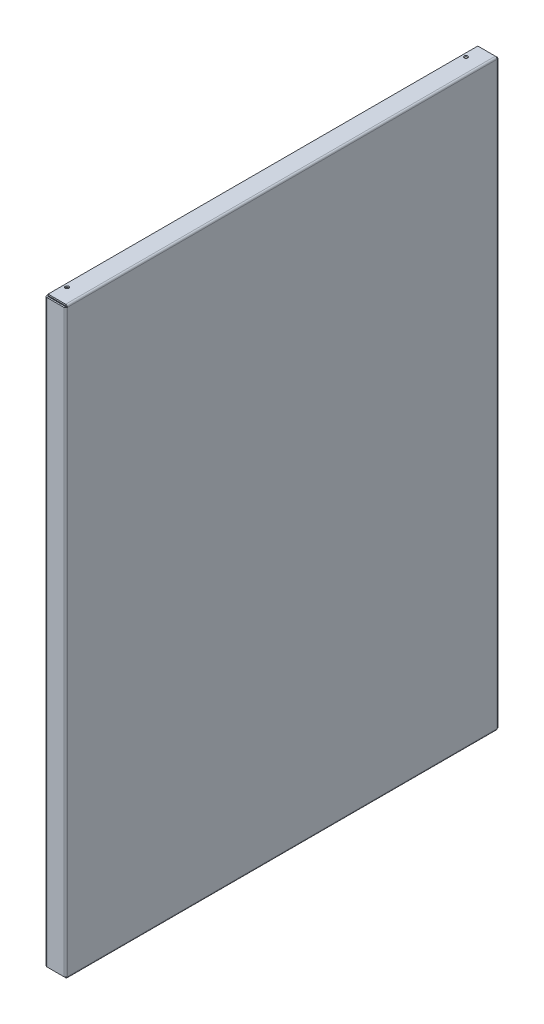
SolidWorks part; units mm, degrees
note: The reader was unsure of these and kept them because the rebuilt part matched: flange length of "Edge-Flange1", "Edge-Flange3", "Edge-Flange4", "Edge-Flange5", "Edge-Flange6", "Edge-Flange7", "Edge-Flange8", "Edge-Flange9".
material "Chrome Stainless Steel"
ref_plane "Front Plane" through (0, 0, 0) normal (0, 0, 1) x (1, 0, 0)
ref_plane "Top Plane" through (0, 0, 0) normal (0, 1, 0) x (1, 0, 0)
ref_plane "Right Plane" through (0, 0, 0) normal (1, 0, 0) x (0, 0, -1)
sketch "Sketch2" plane through (0, 0, 0) normal (1, 0, 0) x (0, 0, -1)
  line L1 (-300, 406) -> (300, 406)
  line L2 (-300, 406) -> (-300, -406)
  line L3 (-300, -406) -> (300, -406)
  line L4 (300, 406) -> (300, -406)
  line L5 (-300, 406) -> (300, -406) construction
  line L6 (-300, -406) -> (300, 406) construction
  point P0 (0, 0)
  dimension "D1" = 600
  dimension "D2" = 812
base flange "Base-Flange1" sketch "Sketch2" thickness 2 reverse thickness direction no parameters "D1"=6.35
edge flange "Edge-Flange1" sketch "Sketch9" flange angle 90 flange length 25 flange position material inside bend radius 0.5 thickness 2 relief rectangular parameters "D6"=10
sketch "Sketch9" plane through (-2, 406, 0) normal (0, -1, 0) x (0, 0, 1)
  line L2 (-300, 0) -> (-300, 25)
  line L3 (-300, 25) -> (300, 25)
  line L4 (300, 25) -> (300, 0)
  line L9 (300, 0) -> (-300, 0) construction
  line L10 (300, 0) -> (-300, 0)
bend "EdgeBend1" bend radius 0.5 bend angle 90 parameters "D5"=1
edge flange "Edge-Flange3" sketch "Sketch15" flange angle 90 flange length 25 flange position bend outside bend radius 0.5 thickness 2 relief rectangular parameters "D6"=10
sketch "Sketch15" plane through (-2, 0, 300) normal (0, 0, 1) x (0, 1, 0)
  line L0 (403.5, 0) -> (-406, 0) construction
  line L1 (403.5, 0) -> (-406, 0)
  line L2 (-406, 0) -> (-406, 25)
  line L3 (-406, 25) -> (403.5, 25)
  line L4 (403.5, 25) -> (403.5, 0)
bend "EdgeBend3" bend radius 0.5 bend angle 90 parameters "D5"=2
edge flange "Edge-Flange4" sketch "Sketch18" flange angle 90 flange length 25 flange position bend outside bend radius 0.5 thickness 2 relief rectangular parameters "D6"=10
sketch "Sketch18" plane through (-2, 0, -300) normal (0, 0, -1) x (0, -1, 0)
  line L2 (-403.5, 0) -> (-403.5, 25)
  line L3 (-403.5, 25) -> (406, 25)
  line L4 (406, 25) -> (406, 0)
  line L11 (406, 0) -> (-403.5, 0) construction
  line L12 (406, 0) -> (-403.5, 0)
bend "EdgeBend4" bend radius 0.5 bend angle 90 parameters "D5"=3
edge flange "Edge-Flange5" sketch "Sketch21" flange angle 90 flange length 25 flange position bend outside bend radius 0.5 thickness 2 relief rectangular parameters "D6"=10
sketch "Sketch21" plane through (-2, -406, 0) normal (0, -1, 0) x (0, 0, 1)
  line L2 (-300, 0) -> (-300, 25)
  line L3 (-300, 25) -> (300, 25)
  line L4 (300, 25) -> (300, 0)
  line L7 (300, 0) -> (-300, 0) construction
  line L8 (300, 0) -> (-300, 0)
bend "EdgeBend5" bend radius 0.5 bend angle 90 parameters "D5"=4
sketch "Sketch22" plane through (0, -408.5, 0) normal (0, -1, 0) x (1, 0, 0)
  line L0 (-27, 300) -> (-27, -300) construction
  line L2 (-2.5, 300) -> (-27, 300) construction
  circle A0 centre (-22, 278.5) radius 2.5
  dimension "D1" = 5
  dimension "D2" = 5
  dimension "D3" = 21.5
extrude "Cut-Extrude1" cut sketch "Sketch22" against normal through all normal cut yes
sketch "Sketch23" plane through (0, 406, 0) normal (0, 1, 0) x (1, 0, 0)
  line L1 (-27, 300) -> (-2.5, 300) construction
  line L3 (-27, -300) -> (-27, 300) construction
  circle A0 centre (-22, 278.5) radius 2.5
  dimension "D1" = 5
  dimension "D2" = 21.5
  dimension "D3" = 5
extrude "Cut-Extrude2" cut sketch "Sketch23" against normal through all normal cut yes
sketch "Sketch24" plane through (0, 0, -302.5) normal (0, 0, -1) x (-1, 0, 0)
  line L0 (27, -406) -> (27, 403.5) construction
  line L1 (2.5, -406) -> (27, -406) construction
  line L2 (27, 403.5) -> (2.5, 403.5) construction
  circle A0 centre (22, 382) radius 2.5
  circle A1 centre (22, -384.5) radius 2.5
  dimension "D1" = 5
  dimension "D4" = 5
  dimension "D2" = 5
  dimension "D3" = 5
  dimension "D5" = 21.5
  dimension "D6" = 21.5
extrude "Cut-Extrude3" cut sketch "Sketch24" against normal blind 25 normal cut yes
edge flange "Edge-Flange6" sketch "Sketch27" flange angle 90 flange length 10 flange position material outside bend radius 1 thickness 2 relief rectangular parameters "D6"=10
sketch "Sketch27" plane through (-27, 0, -300.5) normal (1, 0, 0) x (0, 1, 0)
  line L2 (-406, 0) -> (-406, 10)
  line L3 (-406, 10) -> (403.5, 10)
  line L4 (403.5, 10) -> (403.5, 0)
  line L5 (403.5, 0) -> (-406, 0) construction
  line L6 (403.5, 0) -> (-406, 0)
bend "EdgeBend6" bend radius 1 bend angle 90 parameters "D5"=5
edge flange "Edge-Flange7" sketch "Sketch30" flange angle 90 flange length 20 flange position material outside bend radius 1 thickness 2 relief rectangular parameters "D6"=10
sketch "Sketch30" plane through (-27, 0, -290.5) normal (0, 0, -1) x (0, 1, 0)
  line L2 (-406, 0) -> (-406, 20)
  line L3 (-406, 20) -> (403.5, 20)
  line L4 (403.5, 20) -> (403.5, 0)
  line L9 (403.5, 0) -> (-406, 0) construction
  line L10 (403.5, 0) -> (-406, 0)
bend "EdgeBend7" bend radius 1 bend angle 90 parameters "D5"=6
edge flange "Edge-Flange8" sketch "Sketch33" flange angle 90 flange length 10 flange position material outside bend radius 1 thickness 2 relief rectangular parameters "D6"=10
sketch "Sketch33" plane through (-27, 0, 300.5) normal (1, 0, 0) x (0, -1, 0)
  line L2 (-403.5, 0) -> (-403.5, 10)
  line L3 (-403.5, 10) -> (406, 10)
  line L4 (406, 10) -> (406, 0)
  line L5 (406, 0) -> (-403.5, 0) construction
  line L6 (406, 0) -> (-403.5, 0)
bend "EdgeBend8" bend radius 1 bend angle 90 parameters "D5"=7
edge flange "Edge-Flange9" sketch "Sketch36" flange angle 90 flange length 20 flange position material outside bend radius 1 thickness 2 relief rectangular parameters "D6"=10
sketch "Sketch36" plane through (-27, 0, 290.5) normal (0, 0, 1) x (0, -1, 0)
  line L2 (-403.5, 0) -> (-403.5, 20)
  line L3 (-403.5, 20) -> (406, 20)
  line L4 (406, 20) -> (406, 0)
  line L9 (406, 0) -> (-403.5, 0) construction
  line L10 (406, 0) -> (-403.5, 0)
bend "EdgeBend9" bend radius 1 bend angle 90 parameters "D5"=8
sketch "Bend-Lines1" [suppressed] plane through (0, 0, 0) normal (0, 1, 0) x (1, 0, 0)
sketch "Bounding-Box1" [suppressed] plane through (0, 0, 0) normal (0, 1, 0) x (1, 0, 0)
sheet metal parameters "Sheet-Metal1" thickness 2 parameters "D1"=6.35
flat pattern "Flat-Pattern1" [suppressed]
sketch "Bend-Lines2" plane through (0, 0, 0) normal (0, 1, 0) x (1, 0, 0)
sketch "Bounding-Box2" [suppressed] plane through (0, 0, 0) normal (0, 1, 0) x (1, 0, 0)
sheet metal parameters "Sheet-Metal2" thickness 2 parameters "D1"=6.35
flat pattern "Flat-Pattern1" [suppressed]
sketch "Bend-Lines2" plane through (0, 0, 0) normal (0, 1, 0) x (1, 0, 0)
sketch "Bounding-Box2" [suppressed] plane through (0, 0, 0) normal (0, 1, 0) x (1, 0, 0)
bend of the flat pattern "Flatten-<EdgeBend1>1"
sheet metal parameters "Sheet-Metal4" thickness 2 parameters "D1"=6.35
flat pattern "Flat-Pattern1" [suppressed]
sketch "Bend-Lines2" plane through (0, 0, 0) normal (1, 0, 0) x (0, 0, -1)
  line L0 (-305.7727, 406.65) -> (-305.7727, -415) construction
  line L1 (300, 412.4227) -> (-300, 412.4227) construction
  line L2 (-305.7727, 406.65) -> (-305.7727, -415) construction
  line L3 (300, 412.4227) -> (-300, 412.4227) construction
sketch3d "Bounding-Box2" [suppressed]
  line L0 (300, 436.8454, 0) -> (300, -415, 0) construction
  line L1 (-330.1954, 436.8454, 0) -> (-330.1954, -415, 0) construction
  line L2 (300, 436.8454, 0) -> (-330.1954, 436.8454, 0) construction
  line L3 (300, -415, 0) -> (-330.1954, -415, 0) construction
bend of the flat pattern "Flatten-<EdgeBend3>1"
bend of the flat pattern "Flatten-<EdgeBend1>1"
sheet metal parameters "Sheet-Metal5" thickness 2 parameters "D1"=6.35
flat pattern "Flat-Pattern1" [suppressed]
sketch "Bend-Lines2" plane through (0, 0, 0) normal (1, 0, 0) x (0, 0, -1)
  line L0 (-305.7727, 406.65) -> (-305.7727, -415) construction
  line L1 (300, 412.4227) -> (-300, 412.4227) construction
  line L2 (-305.7727, 406.65) -> (-305.7727, -415) construction
  line L3 (300, 412.4227) -> (-300, 412.4227) construction
sketch3d "Bounding-Box2" [suppressed]
  line L0 (300, 436.8454, 0) -> (300, -415, 0) construction
  line L1 (-330.1954, 436.8454, 0) -> (-330.1954, -415, 0) construction
  line L2 (300, 436.8454, 0) -> (-330.1954, 436.8454, 0) construction
  line L3 (300, -415, 0) -> (-330.1954, -415, 0) construction
bend of the flat pattern "Flatten-<EdgeBend4>1"
bend of the flat pattern "Flatten-<EdgeBend3>1"
bend of the flat pattern "Flatten-<EdgeBend1>1"
sheet metal parameters "Sheet-Metal6" thickness 2 parameters "D1"=6.35
flat pattern "Flat-Pattern1" [suppressed]
sketch "Bend-Lines2" plane through (0, 0, 0) normal (1, 0, 0) x (0, 0, -1)
  line L0 (-305.7727, 406.65) -> (-305.7727, -415) construction
  line L1 (300, 412.4227) -> (-300, 412.4227) construction
  line L2 (-305.7727, 406.65) -> (-305.7727, -415) construction
  line L3 (300, 412.4227) -> (-300, 412.4227) construction
  line L4 (-300, -420.7727) -> (300, -420.7727) construction
  line L5 (305.7727, -415) -> (305.7727, 406.65) construction
  line L6 (-300, -420.7727) -> (300, -420.7727) construction
  line L7 (305.7727, -415) -> (305.7727, 406.65) construction
sketch3d "Bounding-Box2" [suppressed]
  line L0 (330.1954, 436.8454, 0) -> (330.1954, -445.1954, 0) construction
  line L1 (-330.1954, 436.8454, 0) -> (-330.1954, -445.1954, 0) construction
  line L2 (330.1954, 436.8454, 0) -> (-330.1954, 436.8454, 0) construction
  line L3 (330.1954, -445.1954, 0) -> (-330.1954, -445.1954, 0) construction
bend of the flat pattern "Flatten-<EdgeBend4>1"
bend of the flat pattern "Flatten-<EdgeBend5>1"
bend of the flat pattern "Flatten-<EdgeBend3>1"
bend of the flat pattern "Flatten-<EdgeBend1>1"
sheet metal parameters "Sheet-Metal7" thickness 2 parameters "D1"=6.35
flat pattern "Flat-Pattern1" [suppressed]
sketch "Bend-Lines2" plane through (0, 0, 0) normal (1, 0, 0) x (0, 0, -1)
  line L0 (-305.7727, 406.65) -> (-305.7727, -415) construction
  line L1 (300, 412.4227) -> (-300, 412.4227) construction
  line L2 (-305.7727, 406.65) -> (-305.7727, -415) construction
  line L3 (300, 412.4227) -> (-300, 412.4227) construction
  line L4 (-300, -420.7727) -> (300, -420.7727) construction
  line L5 (305.7727, -415) -> (305.7727, 406.65) construction
  line L6 (-300, -420.7727) -> (300, -420.7727) construction
  line L7 (305.7727, -415) -> (305.7727, 406.65) construction
sketch3d "Bounding-Box2" [suppressed]
  line L0 (330.1954, 436.8454, 0) -> (330.1954, -445.1954, 0) construction
  line L1 (-330.1954, 436.8454, 0) -> (-330.1954, -445.1954, 0) construction
  line L2 (330.1954, 436.8454, 0) -> (-330.1954, 436.8454, 0) construction
  line L3 (330.1954, -445.1954, 0) -> (-330.1954, -445.1954, 0) construction
bend of the flat pattern "Flatten-<EdgeBend4>1"
bend of the flat pattern "Flatten-<EdgeBend5>1"
bend of the flat pattern "Flatten-<EdgeBend3>1"
bend of the flat pattern "Flatten-<EdgeBend1>1"
sheet metal parameters "Sheet-Metal8" thickness 2 parameters "D1"=6.35
flat pattern "Flat-Pattern1" [suppressed]
sketch "Bend-Lines2" plane through (0, 0, 0) normal (1, 0, 0) x (0, 0, -1)
  line L0 (-305.7727, 406.65) -> (-305.7727, -415) construction
  line L1 (300, 412.4227) -> (-300, 412.4227) construction
  line L2 (-305.7727, 406.65) -> (-305.7727, -415) construction
  line L3 (300, 412.4227) -> (-300, 412.4227) construction
  line L4 (-300, -420.7727) -> (300, -420.7727) construction
  line L5 (305.7727, -415) -> (305.7727, 406.65) construction
  line L6 (-300, -420.7727) -> (300, -420.7727) construction
  line L7 (305.7727, -415) -> (305.7727, 406.65) construction
sketch3d "Bounding-Box2" [suppressed]
  line L0 (330.1954, 436.8454, 0) -> (330.1954, -445.1954, 0) construction
  line L1 (-330.1954, 436.8454, 0) -> (-330.1954, -445.1954, 0) construction
  line L2 (330.1954, 436.8454, 0) -> (-330.1954, 436.8454, 0) construction
  line L3 (330.1954, -445.1954, 0) -> (-330.1954, -445.1954, 0) construction
bend of the flat pattern "Flatten-<EdgeBend4>1"
bend of the flat pattern "Flatten-<EdgeBend5>1"
bend of the flat pattern "Flatten-<EdgeBend3>1"
bend of the flat pattern "Flatten-<EdgeBend1>1"
sheet metal parameters "Sheet-Metal9" thickness 2 parameters "D1"=6.35
flat pattern "Flat-Pattern1"
sketch "Bend-Lines2" plane through (0, 0, 0) normal (1, 0, 0) x (0, 0, -1)
  line L0 (-301.1781, 412.5) -> (-301.1781, -415) construction
  line L1 (300, 413.6781) -> (-300, 413.6781) construction
  line L2 (-301.1781, 412.5) -> (-301.1781, -415) construction
  line L3 (300, 413.6781) -> (-300, 413.6781) construction
  line L4 (-300, -416.1781) -> (300, -416.1781) construction
  line L5 (301.1781, -415) -> (301.1781, 412.5) construction
  line L6 (-300, -416.1781) -> (300, -416.1781) construction
  line L7 (301.1781, -415) -> (301.1781, 412.5) construction
sketch3d "Bounding-Box2" [suppressed]
  line L0 (326.8562, 439.3562, 0) -> (326.8562, -441.8562, 0) construction
  line L1 (-326.8562, 439.3562, 0) -> (-326.8562, -441.8562, 0) construction
  line L2 (326.8562, 439.3562, 0) -> (-326.8562, 439.3562, 0) construction
  line L3 (326.8562, -441.8562, 0) -> (-326.8562, -441.8562, 0) construction
bend of the flat pattern "Flatten-<EdgeBend4>1"
bend of the flat pattern "Flatten-<EdgeBend5>1"
bend of the flat pattern "Flatten-<EdgeBend3>1"
bend of the flat pattern "Flatten-<EdgeBend1>1"
sheet metal parameters "Sheet-Metal10" thickness 2 parameters "D1"=6.35
flat pattern "Flat-Pattern1" [suppressed]
sketch "Bend-Lines2" plane through (0, 0, 0) normal (1, 0, 0) x (0, 0, -1)
  line L0 (-301.1781, 412.5) -> (-301.1781, -415) construction
  line L1 (300, 413.6781) -> (-300, 413.6781) construction
  line L2 (-301.1781, 412.5) -> (-301.1781, -415) construction
  line L3 (300, 413.6781) -> (-300, 413.6781) construction
  line L4 (-300, -416.1781) -> (300, -416.1781) construction
  line L5 (301.1781, -415) -> (301.1781, 412.5) construction
  line L6 (-300, -416.1781) -> (300, -416.1781) construction
  line L7 (301.1781, -415) -> (301.1781, 412.5) construction
sketch3d "Bounding-Box2" [suppressed]
  line L0 (326.8562, 439.3562, 0) -> (326.8562, -441.8562, 0) construction
  line L1 (-326.8562, 439.3562, 0) -> (-326.8562, -441.8562, 0) construction
  line L2 (326.8562, 439.3562, 0) -> (-326.8562, 439.3562, 0) construction
  line L3 (326.8562, -441.8562, 0) -> (-326.8562, -441.8562, 0) construction
bend of the flat pattern "Flatten-<EdgeBend4>1"
bend of the flat pattern "Flatten-<EdgeBend5>1"
bend of the flat pattern "Flatten-<EdgeBend3>1"
bend of the flat pattern "Flatten-<EdgeBend1>1"
bend of the flat pattern "Flatten-<EdgeBend6>1"
sheet metal parameters "Sheet-Metal11" thickness 2 parameters "D1"=6.35
flat pattern "Flat-Pattern1" [suppressed]
sketch "Bend-Lines2" plane through (0, 0, 0) normal (1, 0, 0) x (0, 0, -1)
  line L0 (-301.1781, 412.5) -> (-301.1781, -415) construction
  line L1 (300, 413.6781) -> (-300, 413.6781) construction
  line L2 (-301.1781, 412.5) -> (-301.1781, -415) construction
  line L3 (300, 413.6781) -> (-300, 413.6781) construction
  line L4 (-300, -416.1781) -> (300, -416.1781) construction
  line L5 (301.1781, -415) -> (301.1781, 412.5) construction
  line L6 (-300, -416.1781) -> (300, -416.1781) construction
  line L7 (301.1781, -415) -> (301.1781, 412.5) construction
sketch3d "Bounding-Box2" [suppressed]
  line L0 (326.8562, 439.3562, 0) -> (326.8562, -441.8562, 0) construction
  line L1 (-326.8562, 439.3562, 0) -> (-326.8562, -441.8562, 0) construction
  line L2 (326.8562, 439.3562, 0) -> (-326.8562, 439.3562, 0) construction
  line L3 (326.8562, -441.8562, 0) -> (-326.8562, -441.8562, 0) construction
bend of the flat pattern "Flatten-<EdgeBend4>1"
bend of the flat pattern "Flatten-<EdgeBend5>1"
bend of the flat pattern "Flatten-<EdgeBend3>1"
bend of the flat pattern "Flatten-<EdgeBend1>1"
bend of the flat pattern "Flatten-<EdgeBend7>1"
bend of the flat pattern "Flatten-<EdgeBend6>1"
sheet metal parameters "Sheet-Metal12" thickness 2 parameters "D1"=6.35
flat pattern "Flat-Pattern1" [suppressed]
sketch "Bend-Lines2" plane through (0, 0, 0) normal (1, 0, 0) x (0, 0, -1)
  line L0 (-301.1781, 412.5) -> (-301.1781, -415) construction
  line L1 (300, 413.6781) -> (-300, 413.6781) construction
  line L2 (-301.1781, 412.5) -> (-301.1781, -415) construction
  line L3 (300, 413.6781) -> (-300, 413.6781) construction
  line L4 (-300, -416.1781) -> (300, -416.1781) construction
  line L5 (301.1781, -415) -> (301.1781, 412.5) construction
  line L6 (-300, -416.1781) -> (300, -416.1781) construction
  line L7 (301.1781, -415) -> (301.1781, 412.5) construction
sketch3d "Bounding-Box2" [suppressed]
  line L0 (326.8562, 439.3562, 0) -> (326.8562, -441.8562, 0) construction
  line L1 (-326.8562, 439.3562, 0) -> (-326.8562, -441.8562, 0) construction
  line L2 (326.8562, 439.3562, 0) -> (-326.8562, 439.3562, 0) construction
  line L3 (326.8562, -441.8562, 0) -> (-326.8562, -441.8562, 0) construction
bend of the flat pattern "Flatten-<EdgeBend4>1"
bend of the flat pattern "Flatten-<EdgeBend5>1"
bend of the flat pattern "Flatten-<EdgeBend3>1"
bend of the flat pattern "Flatten-<EdgeBend1>1"
bend of the flat pattern "Flatten-<EdgeBend7>1"
bend of the flat pattern "Flatten-<EdgeBend8>1"
bend of the flat pattern "Flatten-<EdgeBend6>1"
sheet metal parameters "Sheet-Metal13" thickness 2 parameters "D1"=6.35
flat pattern "Flat-Pattern1"
sketch "Bend-Lines2" plane through (0, 0, 0) normal (1, 0, 0) x (0, 0, -1)
  line L0 (-301.1781, 403.5) -> (-301.1781, -406) construction
  line L1 (300, 404.6781) -> (-300, 404.6781) construction
  line L2 (-301.1781, 403.5) -> (-301.1781, -406) construction
  line L3 (300, 404.6781) -> (-300, 404.6781) construction
  line L4 (-300, -407.1781) -> (300, -407.1781) construction
  line L5 (301.1781, -406) -> (301.1781, 403.5) construction
  line L6 (-300, -407.1781) -> (300, -407.1781) construction
  line L7 (301.1781, -406) -> (301.1781, 403.5) construction
  line L8 (-338.5686, 403.5) -> (-338.5686, -406) construction
  line L9 (-327.427, 403.5) -> (-327.427, -406) construction
  line L10 (338.5686, -406) -> (338.5686, 403.5) construction
  line L11 (327.427, -406) -> (327.427, 403.5) construction
  line L12 (-338.5686, 403.5) -> (-338.5686, -406) construction
  line L13 (-327.427, 403.5) -> (-327.427, -406) construction
  line L14 (338.5686, -406) -> (338.5686, 403.5) construction
  line L15 (327.427, -406) -> (327.427, 403.5) construction
sketch3d "Bounding-Box2" [suppressed]
  line L0 (359.1394, 430.3562, 0) -> (359.1394, -432.8562, 0) construction
  line L1 (-359.1394, 430.3562, 0) -> (-359.1394, -432.8562, 0) construction
  line L2 (359.1394, 430.3562, 0) -> (-359.1394, 430.3562, 0) construction
  line L3 (359.1394, -432.8562, 0) -> (-359.1394, -432.8562, 0) construction
bend of the flat pattern "Flatten-<EdgeBend4>1"
bend of the flat pattern "Flatten-<EdgeBend5>1"
bend of the flat pattern "Flatten-<EdgeBend3>1"
bend of the flat pattern "Flatten-<EdgeBend1>1"
bend of the flat pattern "Flatten-<EdgeBend7>1"
bend of the flat pattern "Flatten-<EdgeBend8>1"
bend of the flat pattern "Flatten-<EdgeBend9>1"
bend of the flat pattern "Flatten-<EdgeBend6>1"
